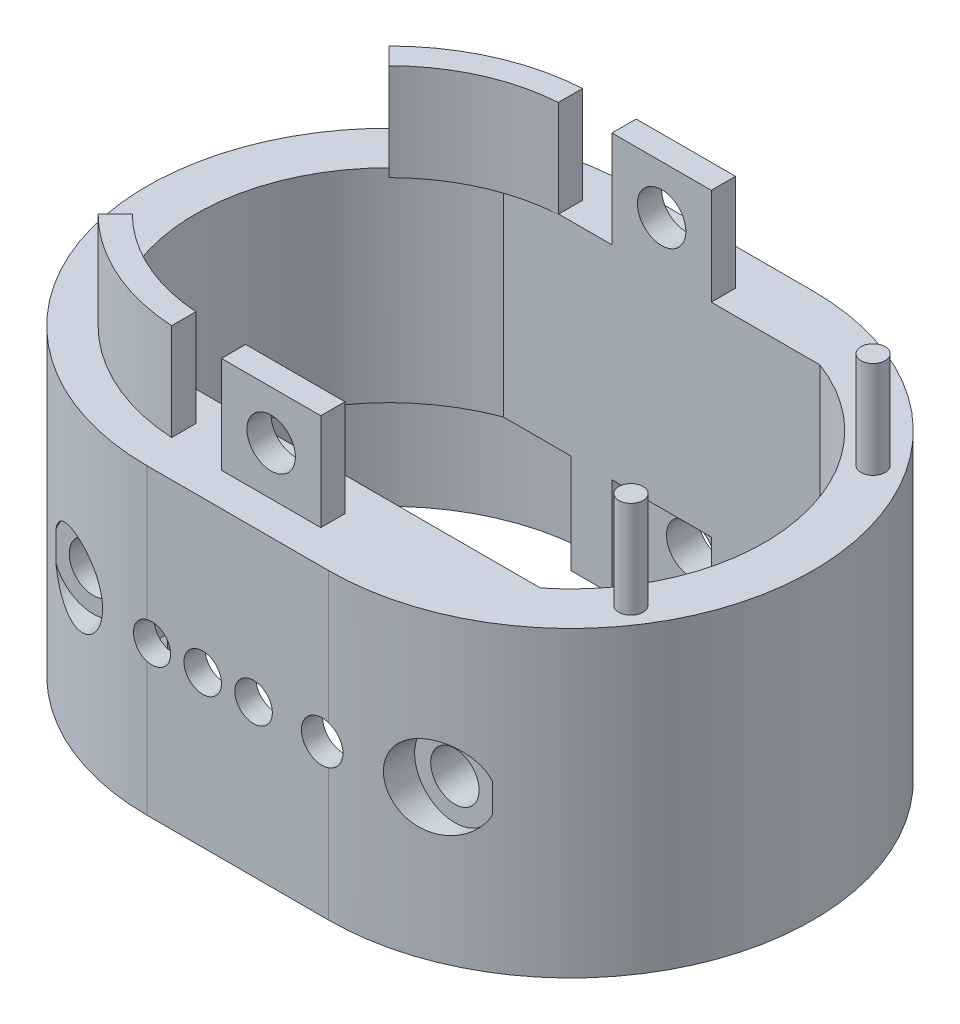
SolidWorks part; units mm, degrees
ref_plane "Front Plane" through (0, 0, 0) normal (0, 0, 1) x (1, 0, 0)
ref_plane "Top Plane" through (0, 0, 0) normal (0, 1, 0) x (1, 0, 0)
ref_plane "Right Plane" through (0, 0, 0) normal (1, 0, 0) x (0, 0, -1)
sketch "Sketch1" plane through (0, 0, 0) normal (0, 1, 0) x (1, 0, 0)
  line L0 (7.5, 0) -> (-7.5, 0) construction
  line L1 (7.5, -20) -> (-7.5, -20)
  line L2 (7.5, 20) -> (-7.5, 20)
  line L3 (-13.0678, 15) -> (13.0678, 15)
  line L5 (-17.4875, -12.5) -> (17.4875, -12.5)
  line L7 (7.5, -16) -> (-7.5, -16) construction
  line L8 (7.5, 16) -> (-7.5, 16) construction
  arc A0 (7.5, -20) -> (7.5, 20) centre (7.5, 0) ccw
  arc A1 (-7.5, 20) -> (-7.5, -20) centre (-7.5, 0) ccw
  arc A2 (-13.0678, 15) -> (-17.4875, -12.5) centre (-7.5, 0) ccw
  arc A3 (17.4875, -12.5) -> (13.0678, 15) centre (7.5, 0) ccw
  arc A4 (-7.5, 16) -> (-7.5, -16) centre (-7.5, 0) ccw construction
  arc A5 (7.5, -16) -> (7.5, 16) centre (7.5, 0) ccw construction
  point P3 (0, 0)
  dimension "D1" = 40
  dimension "D2" = 15
  dimension "D4" = 7.5
  dimension "D5" = 5
  dimension "D3" = 4
extrude "Boss-Extrude1" add sketch "Sketch1" along normal blind 12.5 and the other way blind 12.5
sketch "Sketch3" plane through (0, 0, 20) normal (0, 0, 1) x (1, 0, 0)
  line L0 (-18.5054, 0) -> (-4.3749, 0) construction
  line L1 (-8.65, 12.5) -> (-8.65, -12.5) construction
  line L2 (2.85, -12.5) -> (2.85, 12.5) construction
  line L3 (-7.1, 0) -> (-2.9, 0) construction
  line L4 (-2.9, 0) -> (1.3, 0) construction
  line L5 (8.65, 12.5) -> (8.65, -12.5) construction
  line L6 (-27.5, -12.5) -> (-7.5, -12.5) construction
  line L7 (-7.5, -12.5) -> (7.5, -12.5) construction
  line L8 (-8.65, 12.5) -> (0, 0) construction
  line L9 (0, 0) -> (8.65, 12.5) construction
  circle A0 centre (-7.1, 0) radius 1.55
  circle A1 centre (-2.9, 0) radius 1.55
  circle A2 centre (1.3, 0) radius 1.55
  circle A3 centre (6.95, 0) radius 1.7
  point P19 (-8.65, 0)
  point P21 (2.85, 0)
  point P22 (8.65, 0)
  dimension "D2" = 3.1
  dimension "D3" = 3.4
  dimension "D1" = 11.5
  dimension "D4" = 17.3
extrude "Cut-Extrude1" cut sketch "Sketch3" against normal blind 7.5
sketch "Sketch4" plane through (0, 0, 12.5) normal (0, 0, -1) x (-1, 0, 0)
  line L0 (0, 8.875) -> (0, 0) construction
  line L1 (11.425, 8.875) -> (-11.425, 8.875)
  line L2 (11.425, 8.875) -> (11.425, -8.875)
  line L3 (11.425, -8.875) -> (-11.425, -8.875)
  line L4 (-11.425, 8.875) -> (-11.425, -8.875)
  line L5 (0, 0) -> (11.425, 0) construction
  dimension "D1" = 17.75
  dimension "D2" = 22.85
extrude "Cut-Extrude2" cut sketch "Sketch4" against normal blind 5.75
sketch "Sketch5" plane through (0, 0, 12.5) normal (0, 0, -1) x (-1, 0, 0)
  line L0 (0, 0) -> (14.925, 0) construction
  line L1 (11.425, -8.875) -> (11.425, 8.875) construction
  line L2 (0, 0) -> (-14.925, 0) construction
  circle A0 centre (14.925, 0) radius 2
  arc A1 (7.5, -1.4975) -> (7.5, 1.4975) centre (7.1, 0) ccw construction
  arc A2 (-7.5, 1.6086) -> (-7.5, -1.6086) centre (-6.95, 0) ccw construction
  circle A3 centre (-14.925, 0) radius 2
  point P3 (12.925, 0)
  point P5 (8.65, 0)
  point P8 (-8.65, 0)
  dimension "D2" = 4
  dimension "D1" = 1.5
  dimension "D3" = 17.3
  dimension "D4" = 14.925
extrude "Cut-Extrude3" cut sketch "Sketch5" against normal blind 5.75
sketch "Sketch6" plane through (0, 0, 20) normal (0, 0, 1) x (1, 0, 0)
  circle A0 centre (-14.925, 0) radius 3.325
  circle A1 centre (14.925, 0) radius 3.325
  dimension "D1" = 6.65
extrude "Cut-Extrude4" cut sketch "Sketch6" against normal blind 3
sketch "Sketch7" plane through (0, 0, 12.5) normal (0, 0, -1) x (-1, 0, 0)
  circle A0 centre (14.925, 0) radius 4.825
  circle A1 centre (-14.925, 0) radius 4.825
  dimension "D1" = 9.65
extrude "Cut-Extrude5" cut sketch "Sketch7" along normal blind 3
sketch "Sketch9" plane through (0, -12.5, 0) normal (0, -1, 0) x (1, 0, 0)
  line L0 (13.0678, -15) -> (-13.0678, -15) construction
  line L1 (-4.1, -15) -> (4.1, -15)
  line L2 (-4.1, -15) -> (-4.1, -17.4)
  line L3 (-4.1, -17.4) -> (4.1, -17.4)
  line L4 (4.1, -15) -> (4.1, -17.4)
  line L5 (-7.5, 14.9) -> (-7.5, 17.1)
  line L6 (-7.5, -17.1) -> (-7.5, -14.9)
  line L7 (22.4666, 10) -> (22.4666, -10) construction
  line L8 (22.4666, 10) -> (24.1296, 11.1111) construction
  line L9 (20.2481, 9.7204) -> (21.3592, 8.0574) construction
  line L10 (20.8037, 8.8889) -> (22.4666, 10) construction
  line L11 (23.5, 0) -> (22.4666, 0) construction
  line L12 (20.8037, -8.8889) -> (22.4666, -10) construction
  line L13 (22.4666, -10) -> (24.1296, -11.1111) construction
  line L14 (21.3592, -8.0574) -> (20.2481, -9.7204) construction
  arc A0 (-7.5, 14.9) -> (-7.5, -14.9) centre (-7.5, 0) ccw
  arc A1 (-7.5, 17.1) -> (-7.5, -17.1) centre (-7.5, 0) ccw
  arc A2 (-17.4875, 12.5) -> (-13.0678, -15) centre (-7.5, 0) ccw construction
  circle A3 centre (22.4666, 10) radius 1.1
  circle A4 centre (22.4666, -10) radius 1.1
  arc A5 (7.5, -20) -> (7.5, 20) centre (7.5, 0) ccw construction
  arc A7 (13.0678, -15) -> (17.4875, 12.5) centre (7.5, 0) ccw construction
  point P6 (0, -15)
  point P7 (0, -15)
  point P29 (20.8037, 8.8889)
  dimension "D3" = 34.2
  dimension "D4" = 29.8
  dimension "D5" = 2.2
  dimension "D1" = 8.2
  dimension "D2" = 2.4
  dimension "D6" = 20
  dimension "D7" = 2
extrude "Cut-Extrude6" cut sketch "Sketch9" against normal blind 8.2
sketch "Sketch10" plane through (0, 0, -17.4) normal (0, 0, 1) x (1, 0, 0)
  line L0 (4.1, -12.5) -> (0, -8.4) construction
  line L1 (0, -8.4) -> (-4.1, -12.5) construction
  line L2 (0, -8.4) -> (4.1, -4.3) construction
  circle A0 centre (0, -8.4) radius 2
  dimension "D1" = 4
extrude "Cut-Extrude7" cut sketch "Sketch10" against normal blind 8.2
sketch "Sketch11" plane through (0, 12.5, 0) normal (0, 1, 0) x (1, 0, 0)
  line L0 (-8.5, -14.9666) -> (-8.5, -16.9706)
  line L1 (-18.1066, 10.6066) -> (-19.5208, 12.0208)
  line L2 (0, -15.25) -> (0, -12.5) construction
  line L3 (-4.1, 17) -> (4.1, 17)
  line L4 (-4.1, 17) -> (-4.1, 15)
  line L5 (-4.1, 15) -> (4.1, 15)
  line L6 (4.1, 17) -> (4.1, 15)
  line L7 (-4.1, -15.25) -> (4.1, -15.25)
  line L8 (-4.1, -15.25) -> (-4.1, -17.25)
  line L9 (-4.1, -17.25) -> (4.1, -17.25)
  line L10 (4.1, -15.25) -> (4.1, -17.25)
  line L11 (-17.4875, -12.5) -> (17.4875, -12.5) construction
  line L12 (-8.5, 16.9706) -> (-8.5, 14.9666)
  line L13 (-7.5, 0) -> (0, 0) construction
  line L14 (-7.5, -20) -> (7.5, -20) construction
  line L15 (0, -20) -> (0, -17.25) construction
  line L16 (-19.5208, -12.0208) -> (-18.1066, -10.6066)
  arc A0 (-8.5, 16.9706) -> (-19.5208, 12.0208) centre (-7.5, 0) ccw
  arc A1 (-8.5, 14.9666) -> (-18.1066, 10.6066) centre (-7.5, 0) ccw
  circle A2 centre (22.4666, -10) radius 1
  circle A3 centre (22.4666, 10) radius 1
  arc A4 (-19.5208, -12.0208) -> (-8.5, -16.9706) centre (-7.5, 0) ccw
  arc A5 (-18.1066, -10.6066) -> (-8.5, -14.9666) centre (-7.5, 0) ccw
  dimension "D1" = 2
  dimension "D2" = 34
  dimension "D3" = 30
  dimension "D4" = 2
  dimension "D5" = 2
  dimension "D6" = 1
  dimension "D7" = 135
extrude "Boss-Extrude2" add sketch "Sketch11" along normal blind 8
sketch "Sketch13" plane through (0, 0, 0) normal (0, 0, 1) x (1, 0, 0)
  line L0 (0, 16.5) -> (-4.1, 12.5) construction
  line L1 (0, 16.5) -> (4.1, 20.5) construction
  circle A0 centre (0, 16.5) radius 2
  dimension "D1" = 4
extrude "Cut-Extrude8" cut sketch "Sketch13" against normal blind 24 and the other way blind 23
